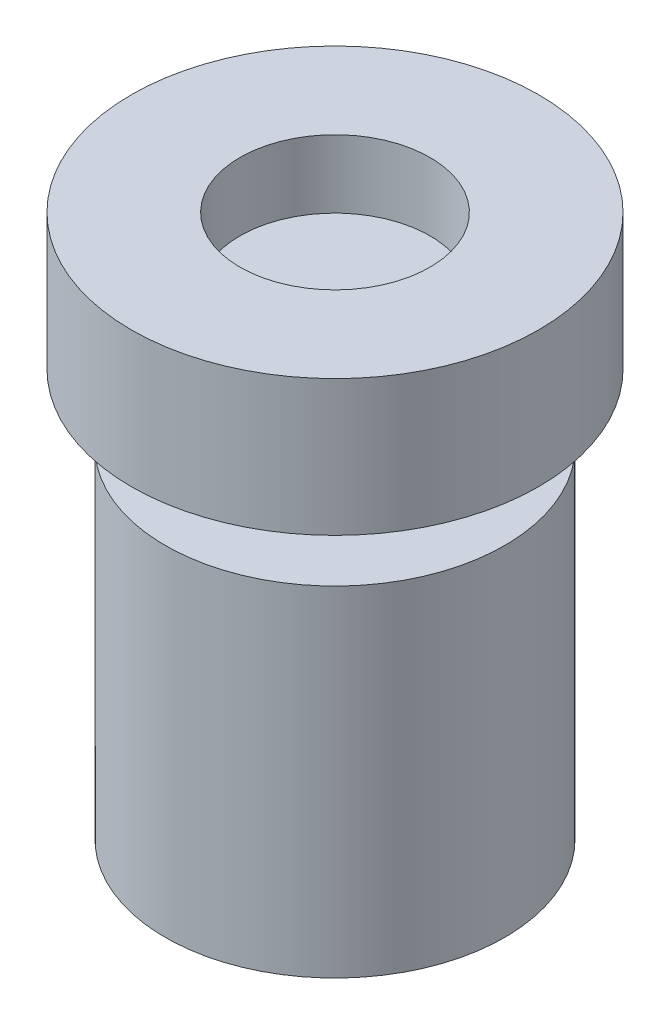
SolidWorks part; units mm, degrees
ref_plane "Front Plane" through (0, 0, 0) normal (0, 0, 1) x (1, 0, 0)
ref_plane "Top Plane" through (0, 0, 0) normal (0, 1, 0) x (1, 0, 0)
ref_plane "Right Plane" through (0, 0, 0) normal (1, 0, 0) x (0, 0, -1)
sketch "Sketch1" plane through (0, 0, 0) normal (0, 1, 0) x (1, 0, 0)
  circle A0 centre (-0.522, 0.5111) radius 1.4
  circle A1 centre (-0.522, 0.5111) radius 3
  dimension "D1" = 2.8
  dimension "D2" = 6
extrude "Boss-Extrude1" add sketch "Sketch1" along normal blind 2
extrude "Boss-Extrude2" add sketch "Sketch1<3>" along normal blind 1 contours A0 region at (-0.522, 0, -0.5111)
sketch "Sketch1<3>" plane through (0, 0, 0) normal (0, 1, 0) x (1, 0, 0) same geometry as "Sketch1"
sketch "Sketch5" plane through (0, 0, 0) normal (0, -1, 0) x (1, 0, 0)
  circle A2 centre (-0.522, -0.5111) radius 1.5
  circle A3 centre (-0.522, -0.5111) radius 1.5
  dimension "D2" = 3
  dimension "D1" = 1.5
extrude "Boss-Extrude3" add sketch "Sketch5" along normal blind 1 contours A3
sketch "Sketch6" plane through (0, -1, 0) normal (0, -1, 0) x (1, 0, 0)
  circle A0 centre (-0.522, -0.5111) radius 2.5
extrude "Boss-Extrude4" add sketch "Sketch6" along normal blind 5
